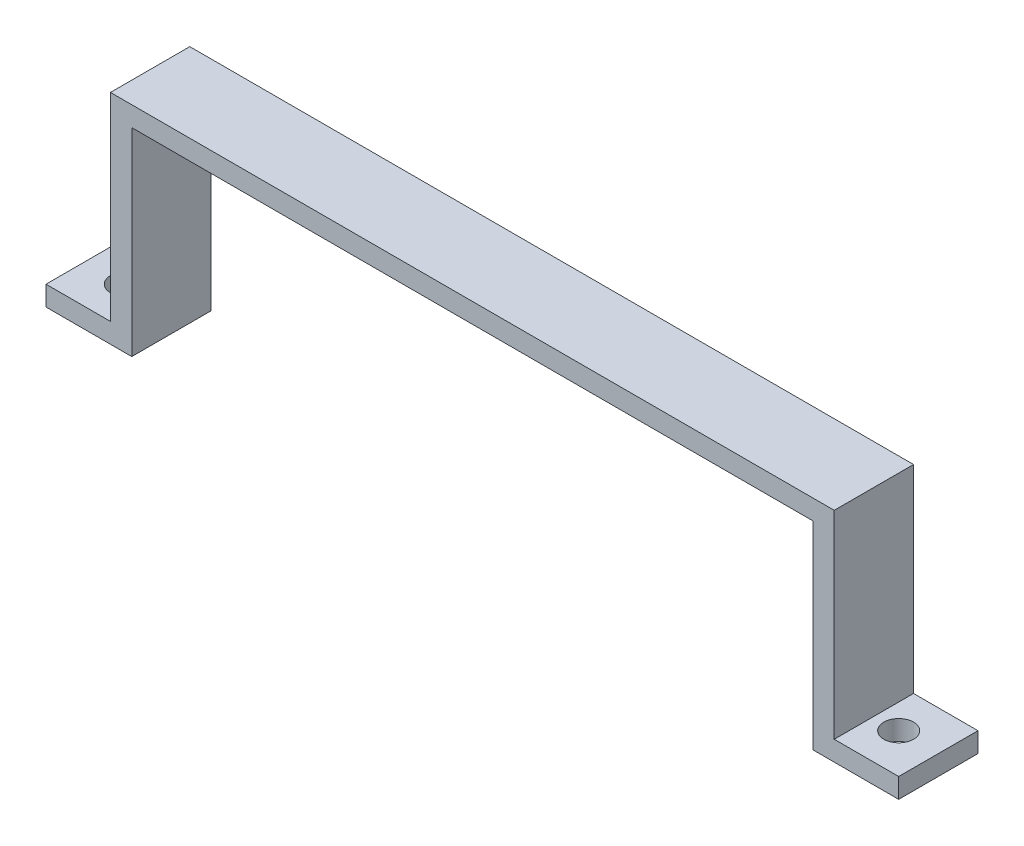
SolidWorks part; units mm, degrees
ref_plane "前视基准面" through (0, 0, 0) normal (0, 0, 1) x (1, 0, 0)
ref_plane "上视基准面" through (0, 0, 0) normal (0, 1, 0) x (1, 0, 0)
ref_plane "右视基准面" through (0, 0, 0) normal (1, 0, 0) x (0, 0, -1)
other "Configuration Table"
sketch "草图1" plane through (0, 0, 0) normal (0, 1, 0) x (1, 0, 0)
  line L0 (34.35, 37) -> (34.35, -78) construction
  line L1 (-36.5, -4) -> (36.5, -4)
  line L2 (-36.5, -4) -> (-36.5, 4)
  line L3 (-36.5, 4) -> (36.5, 4)
  line L4 (36.5, -4) -> (36.5, 4)
  line L5 (-36.5, -4) -> (36.5, 4) construction
  line L6 (-36.5, 4) -> (36.5, -4) construction
  line L23 (-43, 4) -> (-34.35, 4)
  line L24 (-43, 4) -> (-43, -4)
  line L25 (-43, -4) -> (-34.35, -4)
  line L26 (-34.35, 4) -> (-34.35, -4)
  line L27 (34.35, -4) -> (43, -4)
  line L28 (34.35, -4) -> (34.35, 4)
  line L29 (34.35, 4) -> (43, 4)
  line L30 (43, -4) -> (43, 4)
  line L31 (-34.35, 37) -> (-34.35, -78) construction
  circle A0 centre (-39, 0) radius 1.5
  circle A1 centre (39, 0) radius 1.5
  point P0 (0, 0)
  point P20 (0, 0)
  point P21 (-43, 0)
  point P24 (-83.3491, 0)
  point P25 (54.5169, 0)
  point P26 (40.4044, 0)
  dimension "D1" = 73
  dimension "D2" = 8
  dimension "D3" = 8.65
  dimension "D4" = 4
  dimension "D5" = 3
  dimension "D6" = 4
extrude "凸台-拉伸1" add sketch "草图1" along normal blind 2 contours L1 L4 L3 L2
extrude "凸台-拉伸2" add sketch "草图1<15>" against normal blind 20 contours L26 L3 L2 L1 | L28 L1 L4 L3 region at (-35.425, 0, 0) region at (35.425, 0, 0)
sketch "草图1<15>" plane through (0, 0, 0) normal (0, 1, 0) x (1, 0, 0) same geometry as "草图1"
extrude "凸台-拉伸3" add sketch "草图1<16>" along normal blind 2 from surface contours L24 L25 L2 L23 | L27 L30 L29 L4 region at (-39.75, 0, 3.8969) region at (36.6031, 0, 0) starting at face at (-35.425, -20, 0)
sketch "草图1<16>" plane through (0, 0, 0) normal (0, 1, 0) x (1, 0, 0) same geometry as "草图1"
